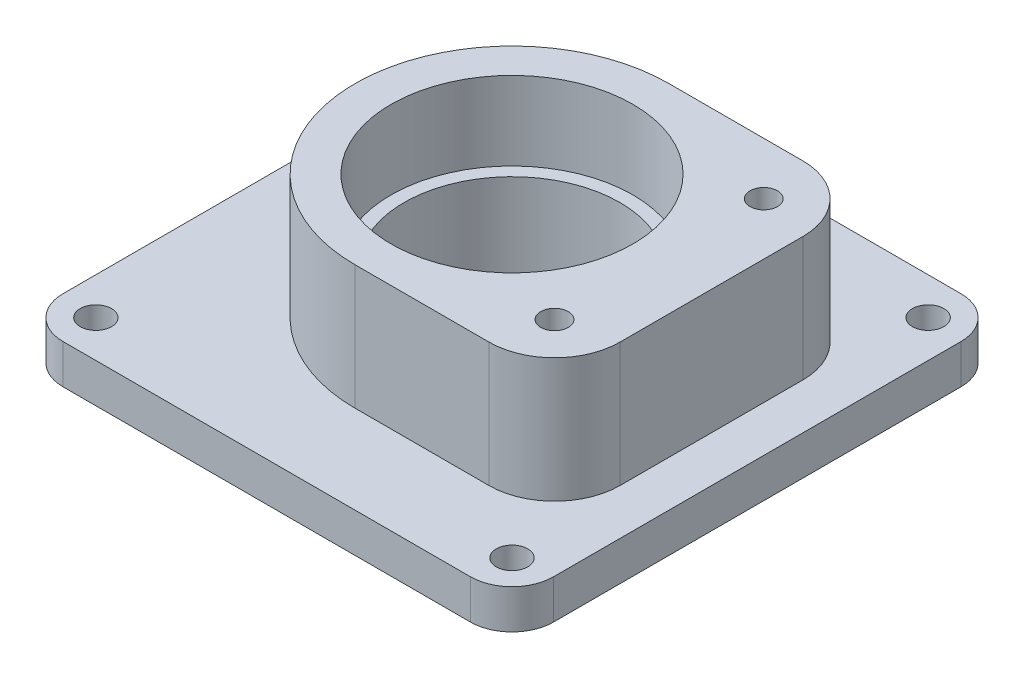
SolidWorks part; units mm, degrees
note: '?' marks a value the reader was unsure of.
ref_plane "Front Plane" through (0, 0, 0) normal (0, 0, 1) x (1, 0, 0)
ref_plane "Top Plane" through (0, 0, 0) normal (0, 1, 0) x (1, 0, 0)
ref_plane "Right Plane" through (0, 0, 0) normal (1, 0, 0) x (0, 0, -1)
ref_axis "X" through (88.99, 0, 0) along (-1, 0, 0)?
ref_axis "Y" through (0, 55, 0) along (0, -1, 0)?
ref_axis "Z" through (0, 0, -88.99) along (0, 0, 1)?
sketch "Sketch1" plane through (0, 0, 0) normal (0, 0, 1) x (1, 0, 0)
  line L0 (0, 0) -> (0, 52.8087) construction
  line L1 (-16.5, 0) -> (-34, 0)
  line L2 (-34, 0) -> (-34, 6)
  line L3 (-34, 6) -> (-24, 6)
  line L4 (-24, 6) -> (-24, 25)
  line L14 (-24, 25) -> (-18.5, 25)
  line L15 (-18.5, 25) -> (-18.5, 13)
  line L21 (-18.5, 13) -> (-16.5, 13)
  line L24 (-16.5, 13) -> (-16.5, 0)
  point P3 (0, 0)
  point P9 (0, 0)
  dimension "D2" = 25
  dimension "D3" = 12
  dimension "D4" = 48
  dimension "D5" = 10
  dimension "D6" = 6
  dimension "D7" = 18.5
  dimension "D10" = 33
revolve "Revolve1" add sketch "Sketch1" angle 360 about L0
sketch "Sketch2" plane through (0, 6, 0) normal (0, 1, 0) x (1, 0, 0)
  line L1 (37.5, -37.5) -> (-37.5, -37.5)
  line L2 (37.5, -37.5) -> (37.5, 37.5)
  line L3 (37.5, 37.5) -> (-37.5, 37.5)
  line L4 (-37.5, -37.5) -> (-37.5, 37.5)
  line L5 (37.5, -37.5) -> (-37.5, 37.5) construction
  line L6 (37.5, 37.5) -> (-37.5, -37.5) construction
  circle A0 centre (0, 0) radius 21
  point P0 (0, 0)
  point P7 (-3.2396, 8.1426)
  dimension "D1" = 75
extrude "Boss-Extrude1" add sketch "Sketch2" against normal up to surface (6 mm away) up to face at (0, 0, -16.5)
hole_wizard "M4 Clearance Hole1" positions "Sketch3" profile "Sketch4" hole size "M4" standard "DIN" end condition up to next
sketch "Sketch3" plane through (0, 0, 0) normal (0, -1, 0) x (-1, 0, 0)
  line L2 (31.8198, -31.8198) -> (-31.8198, -31.8198)
  line L3 (31.8198, -31.8198) -> (31.8198, 31.8198)
  line L4 (31.8198, 31.8198) -> (-31.8198, 31.8198)
  line L5 (-31.8198, -31.8198) -> (-31.8198, 31.8198)
  line L6 (31.8198, -31.8198) -> (-31.8198, 31.8198) construction
  line L7 (31.8198, 31.8198) -> (-31.8198, -31.8198) construction
  point P16 (0, 0)
  point P61 (-31.8198, 31.8198)
  point P64 (31.8198, 31.8198)
  point P67 (31.8198, -31.8198)
  point P70 (-31.8198, -31.8198)
  dimension "D1" = 90
sketch "Sketch4" plane through (0, 0, 0) normal (1, 0, 0) x (0, 0, -1)
  line L0 (0, 0) -> (0, 25)
  line L1 (0, 25) -> (2.4, 25)
  line L2 (2.4, 25) -> (2.4, 0)
  line L5 (2.4, 0) -> (0, 0)
  line L11 (0, -6.35) -> (0, 107.95) construction
  dimension "Thru Hole Dia." = 4.8
  dimension "Thru Hole Depth" = 25
fillet "Fillet1" radius 6.35 4 edges at (37.5, 3, 37.5) (-37.5, 3, 37.5) (37.5, 3, -37.5) (-37.5, 3, -37.5)
sketch "Sketch5" plane through (0, 25, 0) normal (0, 1, 0) x (1, 0, 0)
  line L0 (0, 0) -> (6.5, 0) construction
  line L1 (0, 24) -> (6.5, 24)
  line L2 (0, -24) -> (6.5, -24)
  line L3 (6.5, 24) -> (30.5, 24)
  line L4 (30.5, 24) -> (30.5, -24)
  line L5 (30.5, -24) -> (6.5, -24)
  arc A0 (0, 24) -> (0, -24) centre (0, 0) ccw
  circle A2 centre (0, 0) radius 24 construction
  circle A3 centre (0, 0) radius 24 construction
  circle A5 centre (0, 0) radius 22.8091
  point P3 (5, 0)
  dimension "D1" = 6.5
extrude "Boss-Extrude2" add sketch "Sketch5" against normal up to surface (19 mm away) up to face at (31.8198, 6, -34.2198)
fillet "Fillet2" radius 10 2 edges at (30.5, 15.5, 24) (30.5, 15.5, -24)
hole_wizard "Ø3.0mm Dowel Hole1" [suppressed] positions "Sketch8" profile "Sketch7" hole size "Ø3.0" standard "DIN"
sketch "Sketch8" plane through (0, 25, 0) normal (0, 1, 0) x (1, 0, 0)
  line L0 (20.5, 24) -> (0, 24) construction
  line L2 (30.5, -14) -> (30.5, 14) construction
  point P0 (24.5, 9)
  point P2 (24.5, -9)
  dimension "D1" = 15
  dimension "D2" = 6
  dimension "D3" = 18
sketch "Sketch7" plane through (24.5, 25, -9) normal (1, 0, 0) x (0, 0, 1)
  line L0 (0, 0) -> (0, 6.9013)
  line L1 (0, 6.9013) -> (1.5, 6)
  line L2 (1.5, 6) -> (1.5, 0)
  line L5 (1.5, 0) -> (0, 0)
  line L10 (0, 6.9013) -> (-1.5, 6) construction
  line L11 (0, -6.35) -> (0, 107.95) construction
  dimension "Hole Dia." = 3
  dimension "Hole Depth" = 6
  dimension "Drill Angle" = 118
hole_wizard "M5 Tapped Hole1" positions "Sketch9" profile "Sketch10" tap size "M5" standard "DIN"
sketch "Sketch9" plane through (0, 25, 0) normal (0, 1, 0) x (1, 0, 0)
  line L1 (30.5, -14) -> (30.5, 14) construction
  line L2 (20.5, 24) -> (0, 24) construction
  line L3 (0, -24) -> (20.5, -24) construction
  point P0 (22.5, 16)
  point P2 (22.5, -16)
  dimension "D1" = 8
  dimension "D2" = 8
  dimension "D3" = 8
sketch "Sketch10" plane through (22.5, 25, -16) normal (1, 0, 0) x (0, 0, 1)
  line L0 (0, 0) -> (0, 13.6618)
  line L1 (0, 13.6618) -> (2.1, 12.4)
  line L2 (2.1, 12.4) -> (2.1, 0)
  line L5 (2.1, 0) -> (0, 0)
  line L10 (0, 13.6618) -> (-2.1, 12.4) construction
  line L11 (0, -6.35) -> (0, 107.95) construction
  dimension "Tap Drill Dia." = 4.2
  dimension "Tap Drill Depth" = 12.4
  dimension "Drill Angle" = 118
cosmetic thread "Hole Thread1" parameters "D1"=10, "D2"=5
cosmetic thread "Hole Thread2" parameters "D1"=10, "D2"=5
